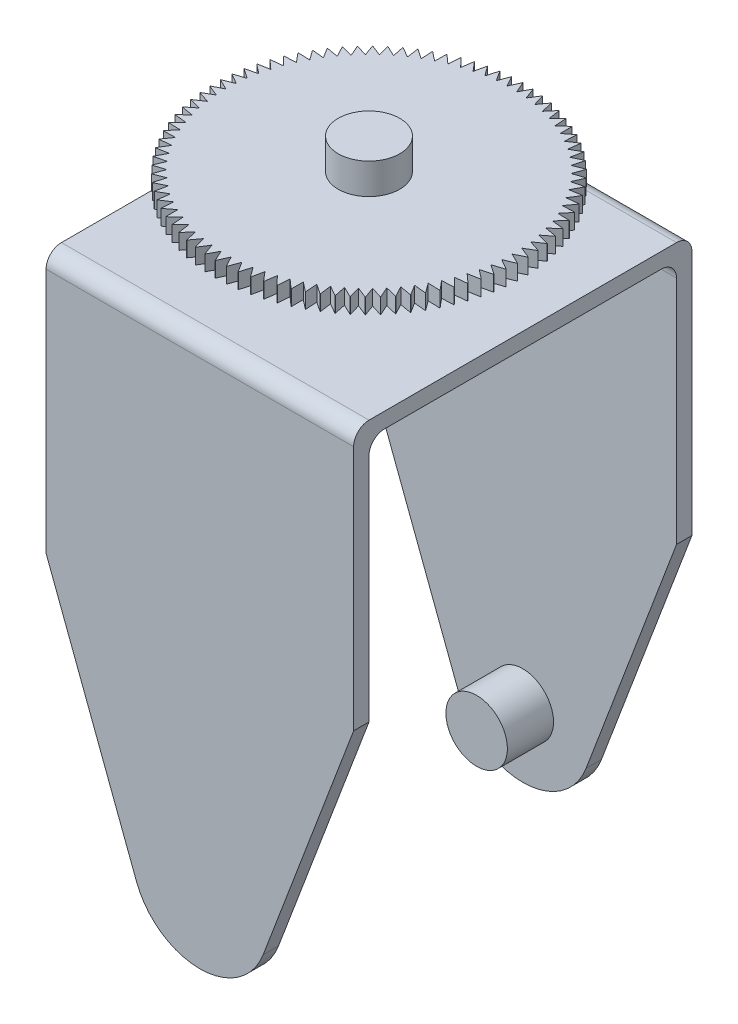
SolidWorks part; units mm, degrees
material "AISI 1035 Steel (SS)"
ref_plane "Front Plane" through (0, 0, 0) normal (0, 0, 1) x (1, 0, 0)
ref_plane "Top Plane" through (0, 0, 0) normal (0, 1, 0) x (1, 0, 0)
ref_plane "Right Plane" through (0, 0, 0) normal (1, 0, 0) x (0, 0, -1)
sketch "Sketch3" plane through (0, 0, 0) normal (0, 0, 1) x (1, 0, 0)
  line L0 (-50, 150) -> (50, 150)
  line L1 (50, 150) -> (50, 70)
  line L2 (50, 70) -> (20.5771, -7.7836)
  line L3 (-50, 150) -> (-50, 70)
  line L4 (-50, 70) -> (-20.5771, -7.7836)
  arc A0 (-20.5771, -7.7836) -> (20.5771, -7.7836) centre (0, 0) ccw
  point P7 (0, 150)
  dimension "D1" = 150
  dimension "D3" = 22
  dimension "D2" = 100
  dimension "D4" = 80
extrude "Boss-Extrude1" add sketch "Sketch3" along normal blind 5
sketch "Sketch4" plane through (0, 0, 5) normal (0, 0, 1) x (1, 0, 0)
  circle A0 centre (0, 0) radius 10
  dimension "D1" = 20
extrude "Boss-Extrude2" add sketch "Sketch4" along normal blind 15
sketch "Sketch5" plane through (0, 0, 0) normal (0, 0, -1) x (-1, 0, 0)
  line L0 (50, 150) -> (50, 70) construction
  line L1 (-50, 150) -> (50, 150)
  line L2 (-50, 150) -> (-50, 155)
  line L3 (-50, 155) -> (50, 155)
  line L4 (50, 150) -> (50, 155)
  dimension "D1" = 5
extrude "Boss-Extrude3" add sketch "Sketch5" against normal blind 55
mirror "Mirror1" about plane through (0, 0, 55) normal (0, 0, 1) of bodies 103
fillet "Fillet1" radius 5 4 edges at (0, 150, 105) (0, 150, 5) (0, 155, 110) (0, 155, 0)
sketch "Sketch6" plane through (0, 155, 0) normal (0, 1, 0) x (1, 0, 0)
  line L0 (50, -5) -> (-50, -5) construction
  line L1 (-50, -105) -> (-50, -5) construction
  circle A0 centre (0, -55) radius 12.5
  point P5 (0, -5)
  point P9 (-50, -55)
  dimension "D1" = 25
extrude "Boss-Extrude4" add sketch "Sketch6" along normal blind 5
sketch "Sketch7" plane through (0, 160, 0) normal (0, 1, 0) x (1, 0, 0)
  circle A0 centre (0, -55) radius 10
  circle A1 centre (0, -55) radius 12.5 construction
  dimension "D1" = 20
extrude "Boss-Extrude5" add sketch "Sketch7" along normal blind 5
sketch "Sketch8" plane through (0, 165, 0) normal (0, 1, 0) x (1, 0, 0)
  circle A0 centre (0, -55) radius 12.5 construction
  circle A1 centre (0, -55) radius 12.5
extrude "Boss-Extrude6" add sketch "Sketch8" along normal blind 5
sketch "Sketch9" plane through (0, 170, 0) normal (0, 1, 0) x (1, 0, 0)
  line L0 (0, -5) -> (1.5929, -8.5336)
  line L1 (1.5929, -8.5336) -> (3.4241, -5.1174)
  line L2 (4.8304, -8.7579) -> (6.8954, -5.4777)
  line L3 (3.4878, -5.1218) -> (4.8304, -8.7579)
  line L4 (8.0443, -9.2075) -> (10.3331, -6.0794)
  line L5 (6.9587, -5.4866) -> (8.0443, -9.2075)
  line L6 (11.219, -9.8802) -> (13.7204, -6.9193)
  line L7 (10.3956, -6.0926) -> (11.219, -9.8802)
  line L8 (14.3391, -10.7727) -> (17.0409, -7.9936)
  line L9 (13.7819, -6.9369) -> (14.3391, -10.7727)
  line L10 (17.3893, -11.8807) -> (20.2784, -9.2968)
  line L11 (17.101, -8.0154) -> (17.3893, -11.8807)
  line L12 (20.3548, -13.1987) -> (23.4171, -10.8227)
  line L13 (20.3368, -9.3227) -> (20.3548, -13.1987)
  line L14 (23.2211, -14.7204) -> (26.4417, -12.5638)
  line L15 (23.4736, -10.8526) -> (23.2211, -14.7204)
  line L16 (25.9743, -16.4384) -> (29.3375, -14.5116)
  line L17 (26.496, -12.5976) -> (25.9743, -16.4384)
  line L18 (28.601, -18.3442) -> (32.0904, -16.6567)
  line L19 (29.3893, -14.5492) -> (28.601, -18.3442)
  line L20 (31.0883, -20.4286) -> (34.6869, -18.9886)
  line L21 (32.1394, -16.6978) -> (31.0883, -20.4286)
  line L22 (33.4241, -22.6814) -> (37.1145, -21.496)
  line L23 (34.7329, -19.033) -> (33.4241, -22.6814)
  line L24 (35.5971, -25.0917) -> (39.3612, -24.1666)
  line L25 (37.1572, -21.5435) -> (35.5971, -25.0917)
  line L26 (37.5967, -27.6477) -> (41.4161, -26.9874)
  line L27 (39.4005, -24.2169) -> (37.5967, -27.6477)
  line L28 (39.4131, -30.3369) -> (43.2693, -29.9447)
  line L29 (41.4519, -27.0404) -> (39.4131, -30.3369)
  line L30 (41.0375, -33.1463) -> (44.9117, -33.024)
  line L31 (43.3013, -30) -> (41.0375, -33.1463)
  line L32 (42.462, -36.0622) -> (46.3352, -36.2104)
  line L33 (44.9397, -33.0814) -> (42.462, -36.0622)
  line L34 (43.6796, -39.0703) -> (47.533, -39.4884)
  line L35 (46.3592, -36.2697) -> (43.6796, -39.0703)
  line L36 (44.6844, -42.156) -> (48.4993, -42.8419)
  line L37 (47.5528, -39.5492) -> (44.6844, -42.156)
  line L38 (45.4715, -45.3044) -> (49.2293, -46.2547)
  line L39 (48.5148, -42.9039) -> (45.4715, -45.3044)
  line L40 (46.0371, -48.4999) -> (49.7194, -49.71)
  line L41 (49.2404, -46.3176) -> (46.0371, -48.4999)
  line L42 (46.3784, -51.7271) -> (49.9673, -53.1912)
  line L43 (49.7261, -49.7736) -> (46.3784, -51.7271)
  line L44 (46.4937, -54.9703) -> (49.9717, -56.6811)
  line L45 (49.9695, -53.255) -> (46.4937, -54.9703)
  line L46 (46.3825, -58.2136) -> (49.7327, -60.1629)
  line L47 (49.9695, -56.745) -> (46.3825, -58.2136)
  line L48 (46.0454, -61.4412) -> (49.2514, -63.6195)
  line L49 (49.7261, -60.2264) -> (46.0454, -61.4412)
  line L50 (45.4839, -64.6375) -> (48.5302, -67.0341)
  line L51 (49.2404, -63.6824) -> (45.4839, -64.6375)
  line L52 (44.7008, -67.7868) -> (47.5725, -70.3901)
  line L53 (48.5148, -67.0961) -> (44.7008, -67.7868)
  line L54 (43.6999, -70.8739) -> (46.3831, -73.6711)
  line L55 (47.5528, -70.4508) -> (43.6999, -70.8739)
  line L56 (42.4862, -73.8835) -> (44.9677, -76.8611)
  line L57 (46.3592, -73.7303) -> (42.4862, -73.8835)
  line L58 (41.0654, -76.8012) -> (43.3332, -79.9446)
  line L59 (44.9397, -76.9186) -> (41.0654, -76.8012)
  line L60 (39.4446, -79.6127) -> (41.4876, -82.9066)
  line L61 (43.3013, -80) -> (39.4446, -79.6127)
  line L62 (37.6317, -82.3043) -> (39.4398, -85.7327)
  line L63 (41.4519, -82.9596) -> (37.6317, -82.3043)
  line L64 (35.6353, -84.8628) -> (37.2, -88.409)
  line L65 (39.4005, -85.7831) -> (35.6353, -84.8628)
  line L66 (33.4654, -87.2759) -> (34.7789, -90.9226)
  line L67 (37.1572, -88.4565) -> (33.4654, -87.2759)
  line L68 (31.1324, -89.5317) -> (32.1883, -93.2611)
  line L69 (34.7329, -90.967) -> (31.1324, -89.5317)
  line L70 (28.6478, -91.6192) -> (29.4409, -95.4133)
  line L71 (32.1394, -93.3022) -> (28.6478, -91.6192)
  line L72 (26.0236, -93.5284) -> (26.5501, -97.3685)
  line L73 (29.3893, -95.4508) -> (26.0236, -93.5284)
  line L74 (23.2726, -95.2499) -> (23.53, -99.1173)
  line L75 (26.496, -97.4024) -> (23.2726, -95.2499)
  line L76 (20.4082, -96.7752) -> (20.3952, -100.6512)
  line L77 (23.4736, -99.1474) -> (20.4082, -96.7752)
  line L78 (17.4444, -98.0971) -> (17.161, -101.9627)
  line L79 (20.3368, -100.6773) -> (17.4444, -98.0971)
  line L80 (14.3956, -99.209) -> (13.8433, -103.0454)
  line L81 (17.101, -101.9846) -> (14.3956, -99.209)
  line L82 (11.2767, -100.1054) -> (10.4581, -103.8941)
  line L83 (13.7819, -103.0631) -> (11.2767, -100.1054)
  line L84 (8.1028, -100.7822) -> (7.0219, -104.5045)
  line L85 (10.3956, -103.9074) -> (8.1028, -100.7822)
  line L86 (4.8895, -101.2359) -> (3.5516, -104.8737)
  line L87 (6.9587, -104.5134) -> (4.8895, -101.2359)
  line L88 (1.6523, -101.4643) -> (0.0639, -105)
  line L89 (3.4878, -104.8782) -> (1.6523, -101.4643)
  line L90 (-1.5929, -101.4664) -> (-3.4241, -104.8826)
  line L91 (0, -105) -> (-1.5929, -101.4664)
  line L92 (-4.8304, -101.2421) -> (-6.8954, -104.5223)
  line L93 (-3.4878, -104.8782) -> (-4.8304, -101.2421)
  line L94 (-8.0443, -100.7925) -> (-10.3331, -103.9206)
  line L95 (-6.9587, -104.5134) -> (-8.0443, -100.7925)
  line L96 (-11.219, -100.1198) -> (-13.7204, -103.0807)
  line L97 (-10.3956, -103.9074) -> (-11.219, -100.1198)
  line L98 (-14.3391, -99.2273) -> (-17.0409, -102.0064)
  line L99 (-13.7819, -103.0631) -> (-14.3391, -99.2273)
  line L100 (-17.3893, -98.1193) -> (-20.2784, -100.7032)
  line L101 (-17.101, -101.9846) -> (-17.3893, -98.1193)
  line L102 (-20.3548, -96.8013) -> (-23.4171, -99.1773)
  line L103 (-20.3368, -100.6773) -> (-20.3548, -96.8013)
  line L104 (-23.2211, -95.2796) -> (-26.4417, -97.4362)
  line L105 (-23.4736, -99.1474) -> (-23.2211, -95.2796)
  line L106 (-25.9743, -93.5616) -> (-29.3375, -95.4884)
  line L107 (-26.496, -97.4024) -> (-25.9743, -93.5616)
  line L108 (-28.601, -91.6558) -> (-32.0904, -93.3433)
  line L109 (-29.3893, -95.4508) -> (-28.601, -91.6558)
  line L110 (-31.0883, -89.5714) -> (-34.6869, -91.0114)
  line L111 (-32.1394, -93.3022) -> (-31.0883, -89.5714)
  line L112 (-33.4241, -87.3186) -> (-37.1145, -88.504)
  line L113 (-34.7329, -90.967) -> (-33.4241, -87.3186)
  line L114 (-35.5971, -84.9083) -> (-39.3612, -85.8334)
  line L115 (-37.1572, -88.4565) -> (-35.5971, -84.9083)
  line L116 (-37.5967, -82.3523) -> (-41.4161, -83.0126)
  line L117 (-39.4005, -85.7831) -> (-37.5967, -82.3523)
  line L118 (-39.4131, -79.6631) -> (-43.2693, -80.0553)
  line L119 (-41.4519, -82.9596) -> (-39.4131, -79.6631)
  line L120 (-41.0375, -76.8537) -> (-44.9117, -76.976)
  line L121 (-43.3013, -80) -> (-41.0375, -76.8537)
  line L122 (-42.462, -73.9378) -> (-46.3352, -73.7896)
  line L123 (-44.9397, -76.9186) -> (-42.462, -73.9378)
  line L124 (-43.6796, -70.9297) -> (-47.533, -70.5116)
  line L125 (-46.3592, -73.7303) -> (-43.6796, -70.9297)
  line L126 (-44.6844, -67.844) -> (-48.4993, -67.1581)
  line L127 (-47.5528, -70.4508) -> (-44.6844, -67.844)
  line L128 (-45.4715, -64.6956) -> (-49.2293, -63.7453)
  line L129 (-48.5148, -67.0961) -> (-45.4715, -64.6956)
  line L130 (-46.0371, -61.5001) -> (-49.7194, -60.29)
  line L131 (-49.2404, -63.6824) -> (-46.0371, -61.5001)
  line L132 (-46.3784, -58.2729) -> (-49.9673, -56.8088)
  line L133 (-49.7261, -60.2264) -> (-46.3784, -58.2729)
  line L134 (-46.4937, -55.0297) -> (-49.9717, -53.3189)
  line L135 (-49.9695, -56.745) -> (-46.4937, -55.0297)
  line L136 (-46.3825, -51.7864) -> (-49.7327, -49.8371)
  line L137 (-49.9695, -53.255) -> (-46.3825, -51.7864)
  line L138 (-46.0454, -48.5588) -> (-49.2514, -46.3805)
  line L139 (-49.7261, -49.7736) -> (-46.0454, -48.5588)
  line L140 (-45.4839, -45.3625) -> (-48.5302, -42.9659)
  line L141 (-49.2404, -46.3176) -> (-45.4839, -45.3625)
  line L142 (-44.7008, -42.2132) -> (-47.5725, -39.6099)
  line L143 (-48.5148, -42.9039) -> (-44.7008, -42.2132)
  line L144 (-43.6999, -39.1261) -> (-46.3831, -36.3289)
  line L145 (-47.5528, -39.5492) -> (-43.6999, -39.1261)
  line L146 (-42.4862, -36.1165) -> (-44.9677, -33.1389)
  line L147 (-46.3592, -36.2697) -> (-42.4862, -36.1165)
  line L148 (-41.0654, -33.1988) -> (-43.3332, -30.0554)
  line L149 (-44.9397, -33.0814) -> (-41.0654, -33.1988)
  line L150 (-39.4446, -30.3873) -> (-41.4876, -27.0934)
  line L151 (-43.3013, -30) -> (-39.4446, -30.3873)
  line L152 (-37.6317, -27.6957) -> (-39.4398, -24.2673)
  line L153 (-41.4519, -27.0404) -> (-37.6317, -27.6957)
  line L154 (-35.6353, -25.1372) -> (-37.2, -21.591)
  line L155 (-39.4005, -24.2169) -> (-35.6353, -25.1372)
  line L156 (-33.4654, -22.7241) -> (-34.7789, -19.0774)
  line L157 (-37.1572, -21.5435) -> (-33.4654, -22.7241)
  line L158 (-31.1324, -20.4683) -> (-32.1883, -16.7389)
  line L159 (-34.7329, -19.033) -> (-31.1324, -20.4683)
  line L160 (-28.6478, -18.3808) -> (-29.4409, -14.5867)
  line L161 (-32.1394, -16.6978) -> (-28.6478, -18.3808)
  line L162 (-26.0236, -16.4716) -> (-26.5501, -12.6315)
  line L163 (-29.3893, -14.5492) -> (-26.0236, -16.4716)
  line L164 (-23.2726, -14.7501) -> (-23.53, -10.8827)
  line L165 (-26.496, -12.5976) -> (-23.2726, -14.7501)
  line L166 (-20.4082, -13.2248) -> (-20.3952, -9.3488)
  line L167 (-23.4736, -10.8526) -> (-20.4082, -13.2248)
  line L168 (-17.4444, -11.9029) -> (-17.161, -8.0373)
  line L169 (-20.3368, -9.3227) -> (-17.4444, -11.9029)
  line L170 (-14.3956, -10.791) -> (-13.8433, -6.9546)
  line L171 (-17.101, -8.0154) -> (-14.3956, -10.791)
  line L172 (-11.2767, -9.8946) -> (-10.4581, -6.1059)
  line L173 (-13.7819, -6.9369) -> (-11.2767, -9.8946)
  line L174 (-8.1028, -9.2178) -> (-7.0219, -5.4955)
  line L175 (-10.3956, -6.0926) -> (-8.1028, -9.2178)
  line L176 (-4.8895, -8.7641) -> (-3.5516, -5.1263)
  line L177 (-6.9587, -5.4866) -> (-4.8895, -8.7641)
  line L178 (-1.6523, -8.5357) -> (-0.0639, -5)
  line L179 (-3.4878, -5.1218) -> (-1.6523, -8.5357)
  circle A0 centre (0, -55) radius 50
  point P276 (0, -55)
  circle M3 centre (0, -55) radius 12.5
  dimension "D1" = 100
  dimension "D2" = 90
  dimension "D3" = 3.876
extrude "Boss-Extrude7" add sketch "Sketch9" along normal blind 5 contours L91 A0 L88 L89 L86 L87 L84 L85 L82 L83 L80 L81 L78 L79 L76 L77 L74 L75 L72 L73 L70 L71 L68 L69 L66 L67 L64 L65 L62 L63 L60 L61 L58 L59 L56 | M3 region at (-0.4924, 170, 7.3478) region at (0, 170, 55)
sketch "Sketch10" plane through (0, 175, 0) normal (0, 1, 0) x (1, 0, 0)
  circle A0 centre (0, -55) radius 10
  circle A1 centre (0, -55) radius 10 construction
  dimension "D1" = 20
extrude "Boss-Extrude8" add sketch "Sketch10" along normal blind 10
